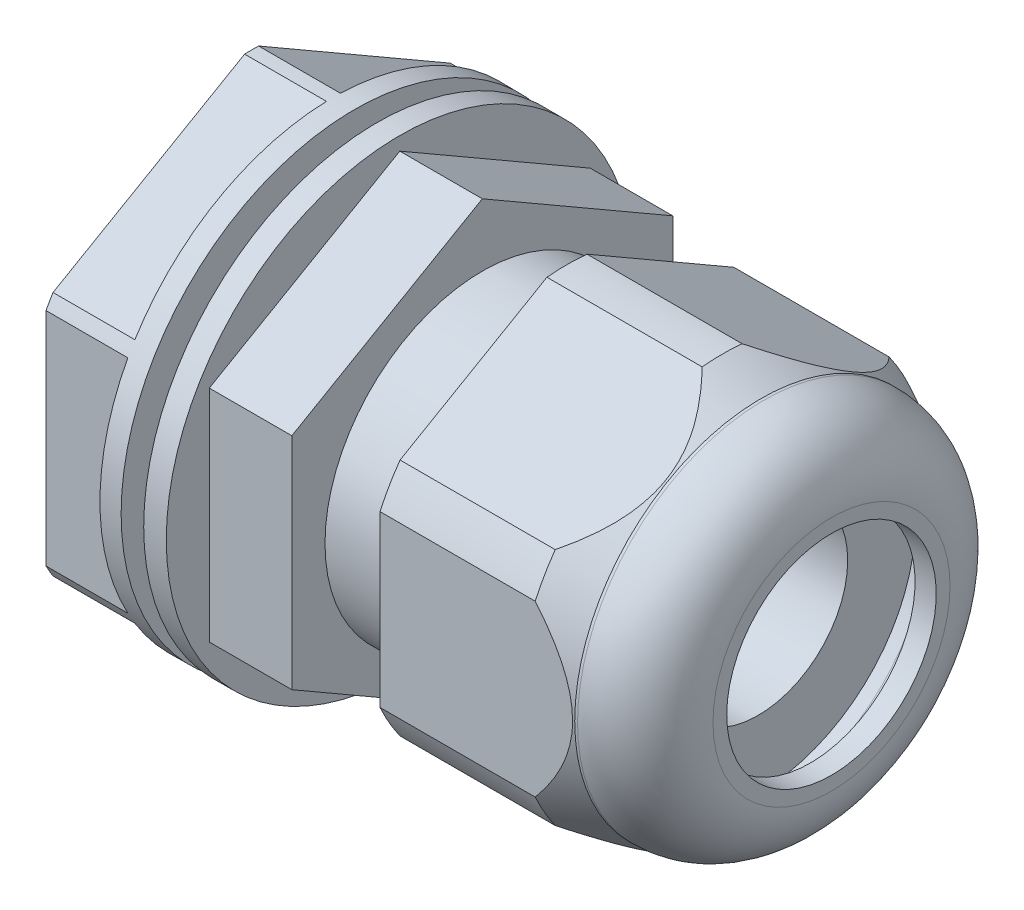
SolidWorks part; units mm, degrees
ref_plane "Front" through (0, 0, 0) normal (0, 0, 1) x (1, 0, 0)
ref_plane "Top" through (0, 0, 0) normal (0, 1, 0) x (1, 0, 0)
ref_plane "Right" through (0, 0, 0) normal (1, 0, 0) x (0, 0, -1)
sketch "Sketch1" plane through (0, 0, 0) normal (1, 0, 0) x (0, 0, -1)
  circle A0 centre (0, 0) radius 11.15
  dimension "\"c\"D1" = 22.3
extrude "Boss-Extrude1" add sketch "Sketch1" along normal blind 10.8
sketch "Sketch2" plane through (10.8, 0, 0) normal (1, 0, 0) x (0, 0, -1)
  line L1 (0, -15.5885) -> (13.5, -7.7942)
  line L2 (13.5, -7.7942) -> (13.5, 7.7942)
  line L3 (13.5, 7.7942) -> (0, 15.5885)
  line L4 (0, 15.5885) -> (-13.5, 7.7942)
  line L5 (-13.5, 7.7942) -> (-13.5, -7.7942)
  line L6 (-13.5, -7.7942) -> (0, -15.5885)
  circle A0 centre (0, 0) radius 13.5 construction
  dimension "\"hex\"D1" = 27
extrude "Boss-Extrude2" add sketch "Sketch2" along normal blind 5.85
sketch "Sketch3" plane through (16.65, 0, 0) normal (1, 0, 0) x (0, 0, -1)
  circle A0 centre (0, 0) radius 11.15
  dimension "\"body2\"D1" = 22.3
extrude "Boss-Extrude3" add sketch "Sketch3" along normal offset from surface (19.55 mm away) 36.2 up to face at (0, 0, -11.15)
sketch "Sketch4" plane through (10.8, 0, 0) normal (-1, 0, 0) x (0, 0, 1)
  circle A0 centre (0, 0) radius 16.55
  dimension "\"gasket diameter\"D1" = 33.1
extrude "Boss-Extrude4" add sketch "Sketch4" along normal blind 1.6
ref_plane "Plane1" through (7.6, 0, 0) normal (-1, 0, 0) x (0, 0, 1)
sketch "Sketch5" plane through (7.6, 0, 0) normal (-1, 0, 0) x (0, 0, 1)
  circle A0 centre (0, 0) radius 16.55
  dimension "\"H\"D1" = 33.1
extrude "Boss-Extrude5" add sketch "Sketch5" along normal blind 7.3
sketch "Sketch6" plane through (0.3, 0, 0) normal (-1, 0, 0) x (0, 0, 1)
  line L1 (0, -16.8298) -> (14.575, -8.4149)
  line L2 (14.575, -8.4149) -> (14.575, 8.4149)
  line L3 (14.575, 8.4149) -> (0, 16.8298)
  line L4 (0, 16.8298) -> (-14.575, 8.4149)
  line L5 (-14.575, 8.4149) -> (-14.575, -8.4149)
  line L6 (-14.575, -8.4149) -> (0, -16.8298)
  circle A0 centre (0, 0) radius 14.575 construction
  circle A1 centre (0, 0) radius 19.575
  dimension "\"NUT DIA\"D1" = 29.15
  dimension "D2" = 5
extrude "Cut-Extrude1" cut sketch "Sketch6" against normal offset from surface (5.8 mm away) 1.5 up to face at (7.6, 0, 16.55)
sketch "Sketch7" plane through (0, 0, 0) normal (-1, 0, 0) x (0, 0, 1)
  circle A0 centre (0, 0) radius 8.5
  dimension "\"B\"D1" = 17
extrude "Cut-Extrude2" cut sketch "Sketch7" against normal offset from surface (24.7 mm away) 11.5 up to face at (36.2, 0, -11.15)
sketch "Sketch8" plane through (36.2, 0, 0) normal (1, 0, 0) x (0, 0, -1)
  circle A0 centre (0, 0) radius 6.35
  dimension "\"A\"D1" = 12.7
extrude "Cut-Extrude3" cut sketch "Sketch8" against normal up to surface (11.5 mm away) up to face at (24.7, 0, -8.5)
sketch "Sketch9" plane through (0, 0, 0) normal (0, 0, 1) x (1, 0, 0)
  line L0 (22.65, 14.55) -> (33.65, 14.55)
  line L1 (33.65, 14.55) -> (36.4, 13.2)
  line L2 (36.4, 13.2) -> (36.6, 13.2)
  line L3 (41.4, 8.4) -> (41.4, 7.425)
  line L4 (22.65, 14.55) -> (22.65, 11.15)
  line L5 (36.2, 11.15) -> (16.65, 11.15) construction
  line L6 (22.65, 11.15) -> (37.15, 11.15)
  line L7 (39.9, 8.4) -> (39.9, 7.425)
  line L8 (39.9, 7.425) -> (41.4, 7.425)
  line L9 (0, 0) -> (59.2195, 0) construction
  line L11 (16.65, 7.7942) -> (16.65, 15.5885) construction
  arc A0 (41.4, 8.4) -> (36.6, 13.2) centre (36.6, 8.4) ccw
  arc A1 (39.9, 8.4) -> (37.15, 11.15) centre (37.15, 8.4) ccw
  dimension "D6" = 4.8
  dimension "\"OD COLLET\"D1" = 29.1
  dimension "\"C_LENGTH\"D2" = 24.75
  dimension "\"ID COLLET\"D3" = 14.85
  dimension "D4" = 13.75
  dimension "D5" = 6
  dimension "\"OD2\"D7" = 26.4
  dimension "D8" = 2.75
  dimension "D10" = 1.5
revolve "Revolve1" add sketch "Sketch9" angle 360 about L9
sketch "Sketch10" plane through (41.4, 0, 0) normal (1, 0, 0) x (0, 0, -1)
  line L1 (13.25, -7.6499) -> (13.25, 7.6499)
  line L2 (13.25, 7.6499) -> (0, 15.2998)
  line L3 (0, 15.2998) -> (-13.25, 7.6499)
  line L4 (-13.25, 7.6499) -> (-13.25, -7.6499)
  line L5 (-13.25, -7.6499) -> (0, -15.2998)
  line L6 (0, -15.2998) -> (13.25, -7.6499)
  circle A0 centre (0, 0) radius 13.25 construction
  circle A1 centre (0, 0) radius 18.25
  dimension "\"COLLET HEX\"D1" = 26.5
  dimension "D2" = 5
extrude "Cut-Extrude4" cut sketch "Sketch10" against normal up to surface (18.75 mm away) up to face at (22.65, 0, -11.15)
